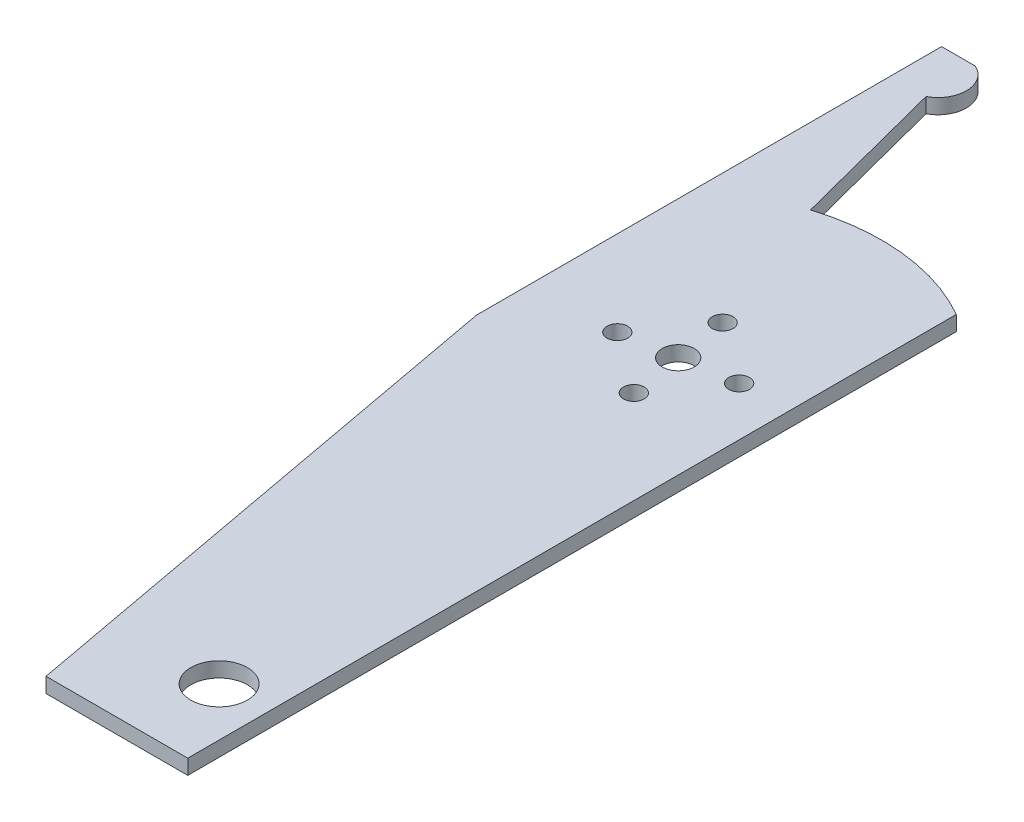
SolidWorks part; units mm, degrees
ref_plane "Front" through (0, 0, 0) normal (0, 0, 1) x (1, 0, 0)
ref_plane "Top" through (0, 0, 0) normal (0, 1, 0) x (1, 0, 0)
ref_plane "Right" through (0, 0, 0) normal (1, 0, 0) x (0, 0, -1)
sketch "Sketch1" plane through (0, 0, 0) normal (0, 1, 0) x (1, 0, 0)
  line L1 (0, 0) -> (50.8, 0)
  line L2 (0, 0) -> (0, 210.82)
  line L3 (0, 210.82) -> (50.8, 210.82)
  line L4 (50.8, 0) -> (50.8, 210.82)
  dimension "D1" = 50.8
  dimension "D2" = 210.82
extrude "Boss-Extrude1" add sketch "Sketch1" along normal blind 3.175
sketch "Sketch2" plane through (0, 3.175, 0) normal (0, 1, 0) x (1, 0, 0)
  line L0 (20.7066, 0) -> (0, 112.0901)
  line L1 (0, 0) -> (50.8, 0) construction
  line L2 (0, 210.82) -> (0, 0) construction
  line L3 (0, 112.0901) -> (0, 0)
  line L4 (0, 0) -> (20.7066, 0)
sketch "Sketch3" plane through (0, 3.175, 0) normal (0, 1, 0) x (1, 0, 0)
  circle A0 centre (40.4364, 127.4091) radius 2.2
  circle A1 centre (31.0117, 114.4794) radius 2.2
  circle A2 centre (27.5067, 136.8337) radius 2.2
  circle A3 centre (18.0821, 123.904) radius 2.2
  circle A4 centre (29.244, 125.665) radius 3.4
  dimension "D1" = 11.303
  dimension "D2" = 11.3
extrude "Cut-Extrude1" cut sketch "Sketch3" against normal blind 10
sketch "Sketch4" plane through (0, 3.175, 0) normal (0, 1, 0) x (1, 0, 0)
  circle A0 centre (40.4628, 16.9889) radius 6
extrude "Cut-Extrude2" cut sketch "Sketch4" against normal blind 10
sketch "Sketch5" plane through (0, 0, 0) normal (0, -1, 0) x (-1, 0, 0)
  line L0 (-16.1209, 166.8622) -> (-7.5059, 200.0707)
  line L1 (-4.7559, 211.3112) -> (-7.5059, 216.5099)
  line L2 (-7.5059, 216.5099) -> (-63.3273, 213.9106)
  line L3 (-63.3273, 213.9106) -> (-59.2095, 156.8339)
  circle A0 centre (-29.244, 125.665) radius 43.2369
  circle A1 centre (-4.7559, 205.3152) radius 5.996
  line M8 (0, 210.82) -> (-50.8, 210.82)
  line M9 (-50.8, 210.82) -> (-50.8, 0)
extrude "Cut-Extrude3" cut sketch "Sketch5" against normal blind 10 contours A1 A0 L0 M8 M9 | A1 L1 L2 L3 A0 M9 M8 region at (31.1673, 0, -189.7662) region at (55.6992, 0, -160.9149)
extrude "Cut-Extrude4" cut sketch "Sketch2" against normal blind 10
